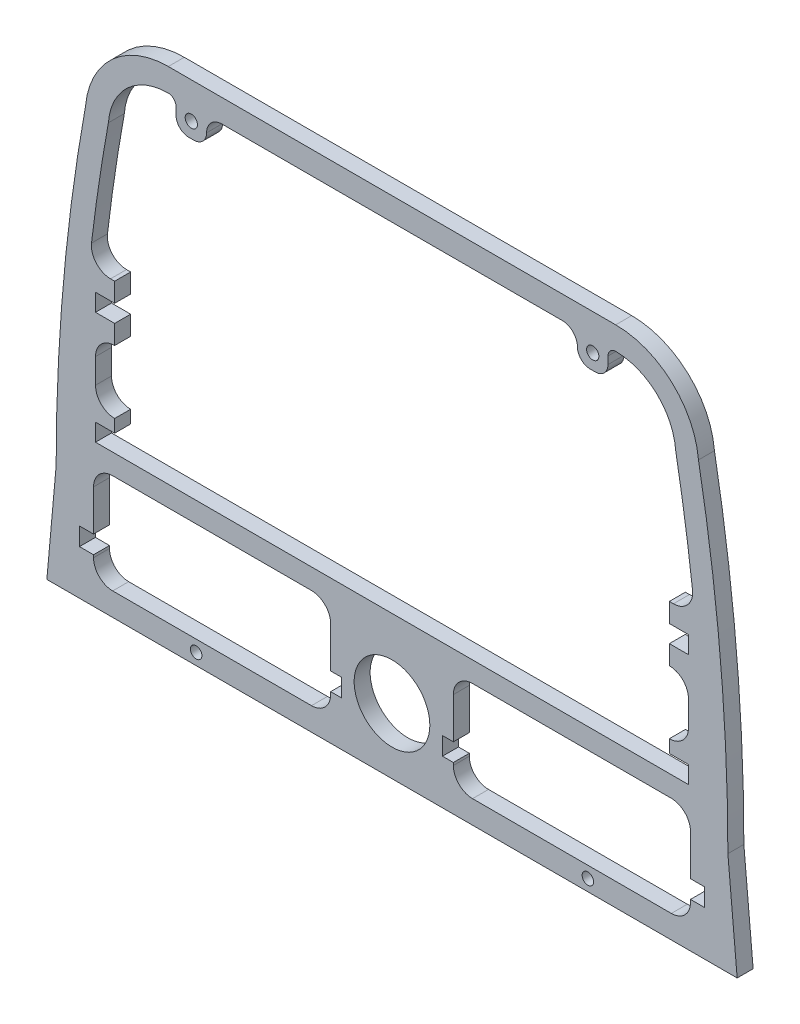
SolidWorks part; units mm, degrees
material "Delrin 2700 NC010, Low Viscosity Acetal Copolymer (SS)"
ref_plane "Front Plane" through (0, 0, 0) normal (0, 0, 1) x (1, 0, 0)
ref_plane "Top Plane" through (0, 0, 0) normal (0, 1, 0) x (1, 0, 0)
ref_plane "Right Plane" through (0, 0, 0) normal (1, 0, 0) x (0, 0, -1)
sketch "Sketch1" plane through (0, 0, 0) normal (0, 0, 1) x (1, 0, 0)
  line L0 (33.3676, -11.9888) -> (34.29, -22.225)
  line L1 (22.225, 27.94) -> (-22.225, 27.94)
  line L2 (-34.29, -22.225) -> (-30.4467, 20.4259) construction
  line L3 (-33.3676, -11.9888) -> (-33.3676, 14.6458) construction
  line L4 (-33.3676, -11.9888) -> (-34.29, -22.225)
  line L5 (16.9079, 25.654) -> (-16.9079, 25.654)
  line L6 (6.096, -17.78) -> (6.096, -19.939)
  line L7 (-29.6529, -19.939) -> (-6.096, -19.939)
  line L8 (-34.29, -22.225) -> (34.29, -22.225)
  line L9 (-29.6529, -10.033) -> (-29.6529, -16.002)
  line L10 (18.4213, 24.1407) -> (18.4213, 24.1363)
  line L11 (19.6913, 22.8663) -> (20.1867, 22.8663)
  line L12 (21.4567, 24.1363) -> (21.4567, 24.8713)
  line L13 (-21.4567, 24.1363) -> (-21.4567, 24.8713)
  line L14 (-19.6913, 22.8663) -> (-20.1867, 22.8663)
  line L15 (-18.4213, 24.1407) -> (-18.4213, 24.1363)
  line L16 (29.4572, -8.001) -> (-29.4572, -8.001)
  line L17 (29.6529, -10.033) -> (6.096, -10.033)
  line L18 (0, 18.415) -> (0, -18.415) construction
  line L19 (-1007.9925, 0) -> (48992.0075, 0) construction
  line L20 (-6.096, -10.033) -> (-29.6529, -10.033)
  line L21 (19.939, 24.384) -> (21.4567, 24.384) construction
  line L22 (6.096, -19.939) -> (29.6529, -19.939)
  line L23 (-6.096, -10.033) -> (-6.096, -16.002)
  line L24 (5.9491, -2.2098) -> (59.5431, -2.2098) construction
  line L25 (5.9491, -2.2098) -> (5.9491, -11.9888) construction
  line L26 (3.4091, -11.9888) -> (-3.4091, -11.9888) construction
  line L27 (59.5431, -2.2098) -> (59.5431, -11.9888) construction
  line L28 (-31.7887, -19.939) -> (31.7887, -19.939) construction
  line L29 (22.225, 25.654) -> (-22.225, 25.654) construction
  line L30 (-6.096, -19.939) -> (-6.1666, -19.9899)
  line L31 (29.4572, -6.2738) -> (27.5522, -6.2738)
  line L32 (27.5522, -6.2738) -> (27.5522, -5.0038)
  line L33 (-29.6529, -16.002) -> (-31.0499, -16.002)
  line L34 (27.5522, -5.0038) -> (29.4572, -5.0038)
  line L35 (29.4572, 1.27) -> (27.5522, 1.27)
  line L36 (27.5522, 1.27) -> (27.5522, 3.175)
  line L37 (27.5522, 3.175) -> (29.4572, 3.175)
  line L38 (29.4572, 4.9022) -> (27.5522, 4.9022)
  line L39 (19.939, 24.384) -> (18.4213, 24.384) construction
  line L40 (27.5522, 4.9022) -> (27.5522, 6.8072)
  line L41 (27.5522, 6.8072) -> (30.0922, 6.8072)
  line L42 (19.939, 24.384) -> (19.939, 22.8663) construction
  line L43 (6.096, -10.033) -> (6.096, -16.002)
  line L44 (-29.4572, -6.2738) -> (-29.4572, -8.001)
  line L45 (-29.4572, -6.2738) -> (-27.5522, -6.2738)
  line L46 (-27.5522, -6.2738) -> (-27.5522, -5.0038)
  line L47 (-27.5522, -5.0038) -> (-29.4572, -5.0038)
  line L48 (-29.4572, 1.27) -> (-29.4572, -5.0038)
  line L49 (-29.4572, 1.27) -> (-27.5522, 1.27)
  line L50 (-27.5522, 1.27) -> (-27.5522, 3.175)
  line L51 (-27.5522, 3.175) -> (-29.4572, 3.175)
  line L52 (-29.4572, 4.9022) -> (-29.4572, 3.175)
  line L53 (-31.0499, -16.002) -> (-31.0499, -17.78)
  line L54 (-31.0499, -17.78) -> (-29.6529, -17.78)
  line L55 (-6.096, -16.002) -> (-5.0149, -16.002)
  line L56 (-5.0149, -16.002) -> (-5.0149, -17.78)
  line L57 (-5.0149, -17.78) -> (-6.096, -17.78)
  line L58 (-29.6529, -10.033) -> (-29.6529, -19.939) construction
  line L59 (-29.6529, -14.986) -> (-33.4249, -14.986) construction
  line L60 (-29.6529, -14.986) -> (-0.4824, -14.986) construction
  line L61 (-6.096, -17.78) -> (-6.096, -19.939)
  line L62 (-29.6529, -19.939) -> (-29.6529, -17.78)
  line L63 (29.6529, -19.939) -> (29.6529, -17.78)
  line L64 (-31.0816, -12.0913) -> (-31.7887, -19.939) construction
  line L65 (29.6529, -10.033) -> (29.6529, -16.002)
  line L66 (31.0499, -17.78) -> (29.6529, -17.78)
  line L67 (31.0499, -16.002) -> (31.0499, -17.78)
  line L68 (29.6529, -16.002) -> (31.0499, -16.002)
  line L69 (6.096, -16.002) -> (5.0149, -16.002)
  line L70 (5.0149, -16.002) -> (5.0149, -17.78)
  line L71 (5.0149, -17.78) -> (6.096, -17.78)
  line L72 (29.4572, 4.9022) -> (29.4572, 3.175)
  line L73 (31.0816, -12.0913) -> (31.7887, -19.939) construction
  line L74 (29.4572, 1.27) -> (29.4572, -5.0038)
  line L75 (29.4572, -6.2738) -> (29.4572, -8.001)
  line L76 (-29.4572, 4.9022) -> (-27.5522, 4.9022)
  line L77 (-27.5522, 4.9022) -> (-27.5522, 6.8072)
  line L78 (-27.5522, 6.8072) -> (-30.0922, 6.8072)
  line L79 (-19.4575, -21.082) -> (-19.4575, -19.939) construction
  line L80 (-19.4575, -21.082) -> (-19.4575, -22.225) construction
  arc A0 (22.225, 27.94) -> (30.4467, 20.4259) centre (22.225, 19.685) cw
  arc A1 (-22.225, 27.94) -> (-30.4467, 20.4259) centre (-22.225, 19.685) ccw
  arc A2 (33.3676, -11.9888) -> (30.4467, 20.4259) centre (-147.9525, -11.9888) ccw
  circle A3 centre (0, -15.748) radius 3.7592
  circle A4 centre (19.4575, -21.082) radius 0.5715
  arc A5 (-33.3676, -11.9888) -> (-30.4467, 20.4259) centre (147.9525, -11.9888) cw
  arc A8 (20.1867, 22.8663) -> (21.4567, 24.1363) centre (20.1867, 24.1363) ccw
  circle A9 centre (-19.939, 24.384) radius 0.6096
  circle A10 centre (19.939, 24.384) radius 0.6096
  arc A11 (18.4213, 24.1363) -> (19.6913, 22.8663) centre (19.6913, 24.1363) ccw
  circle A12 centre (-19.4575, -21.082) radius 0.5715
  arc A13 (18.4213, 24.1407) -> (16.9079, 25.654) centre (16.9079, 24.1407) ccw
  arc A14 (22.2416, 25.654) -> (21.4567, 24.8713) centre (22.2394, 24.8713) ccw
  arc A15 (-22.2416, 25.654) -> (-21.4567, 24.8713) centre (-22.2394, 24.8713) cw
  arc A16 (-20.1867, 22.8663) -> (-21.4567, 24.1363) centre (-20.1867, 24.1363) cw
  arc A17 (-18.4213, 24.1363) -> (-19.6913, 22.8663) centre (-19.6913, 24.1363) cw
  arc A18 (-22.2416, 25.654) -> (-28.1777, 20.1262) centre (-22.225, 19.685) ccw
  arc A19 (-18.4213, 24.1407) -> (-16.9079, 25.654) centre (-16.9079, 24.1407) cw
  arc A20 (31.0816, -12.0913) -> (31.0816, -11.9888) centre (-147.9525, -11.9888) ccw
  arc A23 (22.2416, 25.654) -> (28.1777, 20.1262) centre (22.225, 19.685) cw
  arc A25 (-22.225, 25.654) -> (-28.1777, 20.1262) centre (-22.225, 19.685) ccw construction
  arc A26 (22.225, 25.654) -> (28.1777, 20.1262) centre (22.225, 19.685) cw construction
  arc A28 (-31.0816, -12.0913) -> (-28.1777, 20.1262) centre (147.9525, -11.9888) cw construction
  arc A30 (31.0816, -12.0913) -> (28.1777, 20.1262) centre (-147.9525, -11.9888) ccw construction
  arc A31 (30.0922, 6.8072) -> (28.1777, 20.1262) centre (-147.9525, -11.9888) ccw
  arc A33 (-30.0922, 6.8072) -> (-28.1777, 20.1262) centre (147.9525, -11.9888) cw
  point P0 (0, 0)
  point P1 (0, 27.94)
  point P26 (0, -22.225)
  point P31 (0, -11.9888)
  point P121 (-30.9018, -14.986)
  dimension "D4" = 2.286
  dimension "D6" = 8.255
  dimension "D7" = 19.4575
  dimension "D8" = 50.165
  dimension "D9" = 15.748
  dimension "D5" = 1.2192
  dimension "D17" = 1.143
  dimension "D3" = 7.5184
  dimension "D18" = 1.27
  dimension "D19" = 1.27
  dimension "D26" = 11.176
  dimension "D28" = 0.7827
  dimension "D29" = 1.5133
  dimension "D32" = 1.397
  dimension "D2" = 44.45
  dimension "D11" = 1.27
  dimension "D12" = 68.58
  dimension "D13" = 19.939
  dimension "D14" = 22.225
  dimension "D15" = 53.594
  dimension "D16" = 9.779
  dimension "D20" = 6.096
  dimension "D21" = 11.938
  dimension "D22" = 2.032
  dimension "D23" = 1.7272
  dimension "D24" = 1.27
  dimension "D25" = 1.905
  dimension "D27" = 0.4954
  dimension "D30" = 1.905
  dimension "D31" = 1.7272
  dimension "D33" = 1.778
  dimension "D34" = 2.159
  dimension "D35" = 23.5569
  dimension "D36" = 26.035
  dimension "D37" = 1.905
  dimension "D38" = 2.54
extrude "Boss-Extrude1" add sketch "Sketch1" along normal blind 1.5875 contours L8 A12 A4 L0 A2 A0 L1 A1 A5 L4 L74 L16 A18 A15 L13 A16 L14 A17 L15 A19 L5 A13 L10 A11 L11 A8 L12 A14 A23 A20 L22 L43 L17 A10 A9 A3 L20 region at (32.9825, -17.1832, 0)
ref_axis "Axis1" through (0, -15.748, 0) along (0, 0, 1)
fillet "Fillet1" radius 1.905 8 edges at (-6.096, -10.033, 0.7937) (6.096, -10.033, 0.7937) (-6.096, -19.939, 0.7937) (-29.6529, -19.939, 0.7937) (-29.6529, -10.033, 0.7937) (6.096, -19.939, 0.7937) (29.6529, -19.939, 0.7937) (29.6529, -10.033, 0.7937)
fillet "Fillet2" radius 1.905 6 edges at (-29.4572, 1.27, 0.7937) (-29.4572, -5.0038, 0.7937) (-30.0922, 6.8072, 0.7937) (29.4572, -5.0038, 0.7937) (29.4572, 1.27, 0.7937) (30.0922, 6.8072, 0.7937)
